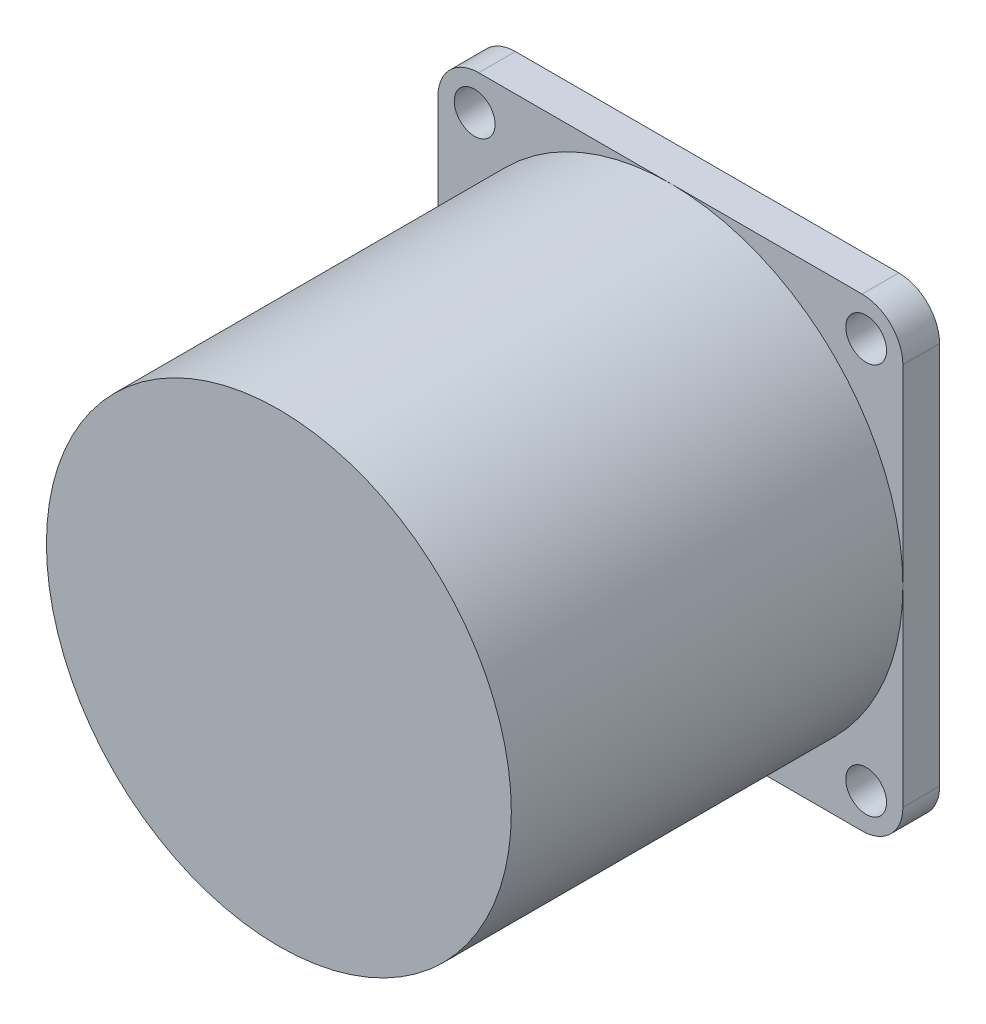
SolidWorks part; units mm, degrees
ref_plane "Plan de face" through (0, 0, 0) normal (0, 0, 1) x (1, 0, 0)
ref_plane "Plan de dessus" through (0, 0, 0) normal (0, 1, 0) x (1, 0, 0)
ref_plane "Plan de droite" through (0, 0, 0) normal (1, 0, 0) x (0, 0, -1)
sketch "Esquisse1" plane through (0, 0, 0) normal (0, 0, 1) x (1, 0, 0)
  line L1 (-30.2986, 21.7084) -> (26.7014, 21.7084)
  line L2 (-30.2986, 21.7084) -> (-30.2986, -35.2916)
  line L3 (-30.2986, -35.2916) -> (26.7014, -35.2916)
  line L4 (26.7014, 21.7084) -> (26.7014, -35.2916)
  circle A0 centre (-25.7986, 17.2084) radius 2.5
  circle A1 centre (22.2014, 17.2084) radius 2.5
  circle A2 centre (22.2014, -30.7916) radius 2.5
  circle A3 centre (-25.7986, -30.7916) radius 2.5
  dimension "D5" = 4.5
  dimension "D4" = 5
  dimension "D1" = 57
  dimension "D2" = 57
  dimension "D3" = 4.5
  dimension "D6" = 4.5
extrude "Boss.-Extru.1" add sketch "Esquisse1" along normal blind 4.5
fillet "Congé2" radius 5 4 edges at (26.7014, -35.2916, 2.25) (-30.2986, 21.7084, 2.25) (-30.2986, -35.2916, 2.25) (26.7014, 21.7084, 2.25)
sketch "Esquisse2" plane through (0, 0, 0) normal (0, 0, -1) x (-1, 0, 0)
  line L0 (-26.7014, -30.2916) -> (-26.7014, 16.7084) construction
  line L2 (-21.7014, 21.7084) -> (25.2986, 21.7084) construction
  circle A0 centre (1.7986, -6.7916) radius 19
  dimension "D3" = 38
  dimension "D1" = 28.5
  dimension "D2" = 28.5
extrude "Boss.-Extru.2" add sketch "Esquisse2" along normal blind 1
chamfer "Chanfrein1" distance 1 angle 45 1 edges at (-20.7986, -6.7916, -1)
sketch "Esquisse3" plane through (0, 0, 4.5) normal (0, 0, 1) x (1, 0, 0)
  line L0 (-25.2986, -35.2916) -> (21.7014, -35.2916) construction
  line L1 (-30.2986, 16.7084) -> (-30.2986, -30.2916) construction
  circle A0 centre (-1.7986, -6.7916) radius 28.5
  dimension "D1" = 28.5
  dimension "D2" = 28.5
  dimension "D3" = 57
extrude "Boss.-Extru.3" add sketch "Esquisse3" along normal blind 48
sketch "Esquisse4" plane through (0, 0, -1) normal (0, 0, -1) x (-1, 0, 0)
  circle A0 centre (1.7986, -6.7916) radius 6.75
  dimension "D1" = 13.5
extrude "Boss.-Extru.4" add sketch "Esquisse4" along normal blind 1.5
sketch "Esquisse5" plane through (0, 0, -2.5) normal (0, 0, -1) x (-1, 0, 0)
  circle A0 centre (1.7986, -6.7916) radius 3
  dimension "D1" = 6
extrude "Boss.-Extru.5" add sketch "Esquisse5" along normal blind 20
